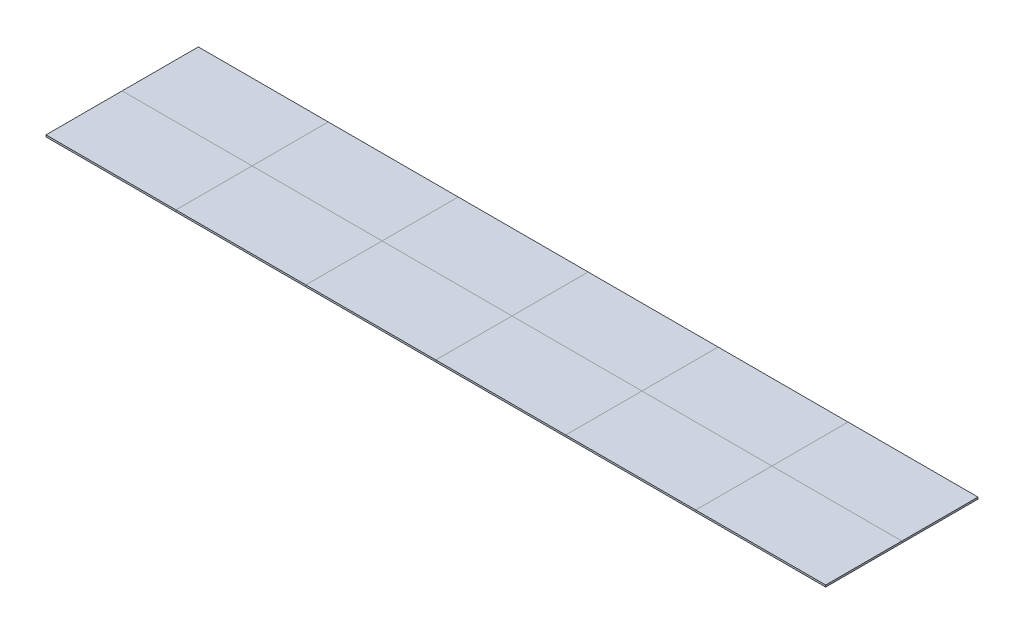
SolidWorks part; units mm, degrees
ref_plane "Front Plane" through (0, 0, 0) normal (0, 0, 1) x (1, 0, 0)
ref_plane "Top Plane" through (0, 0, 0) normal (0, 1, 0) x (1, 0, 0)
ref_plane "Right Plane" through (0, 0, 0) normal (1, 0, 0) x (0, 0, -1)
sketch "Sketch1" plane through (0, 0, 0) normal (0, 1, 0) x (1, 0, 0)
  line L4 (0, 0) -> (12026.9, 0)
  line L5 (12026.9, 0) -> (12026.9, 2349.5)
  line L6 (12026.9, 2349.5) -> (0, 2349.5)
  line L7 (0, 2349.5) -> (0, 0)
  line L8 (0, 0) -> (12026.9, 0)
  line L9 (12026.9, 0) -> (12026.9, 2349.5)
  line L10 (12026.9, 2349.5) -> (0, 2349.5)
  line L11 (0, 2349.5) -> (0, 0)
  dimension "D1" = 0
extrude "Boss-Extrude1" add sketch "Sketch1" along normal blind 27.94
sketch "Sketch3" plane through (0, 0, 0) normal (0, 1, 0) x (1, 0, 0)
  line L0 (0, 1174.75) -> (12026.9, 1174.75)
  line L1 (0, 2349.5) -> (0, 0) construction
  line L2 (12026.9, 0) -> (12026.9, 2349.5) construction
  line L3 (2004.4833, 0) -> (2004.4833, 2349.5)
  line L4 (12026.9, 2349.5) -> (0, 2349.5) construction
  line L5 (4008.9667, 0) -> (4008.9667, 2349.5)
  line L7 (10022.4167, 0) -> (10022.4167, 2349.5)
  line L8 (8017.9333, 0) -> (8017.9333, 2349.5)
  line L9 (6013.45, 0) -> (6013.45, 2349.5)
  point P6 (0, 0)
  point P11 (2004.4833, 1174.75)
  point P14 (4008.9667, 1174.75)
  point P20 (10022.4167, 1174.75)
  point P23 (8017.9333, 1174.75)
  point P27 (6013.45, 1174.75)
  dimension "D1" = 6013.45
  dimension "D2" = 2004.4833
  dimension "D3" = 2004.4833
  dimension "D4" = 2004.4833
  dimension "D5" = 2004.4833
split "Split1" trim tools "Sketch3" bodies to split 101 resulting bodies 102 103 104 105 106 107 108 109 110 111 112 113
equation "\"D2@Sketch3\"=\"D1@Sketch3\"/3"
equation "\"D3@Sketch3\"=\"D2@Sketch3\""
equation "\"D4@Sketch3\"=\"D2@Sketch3\""
equation "\"D5@Sketch3\"=\"D4@Sketch3\""
